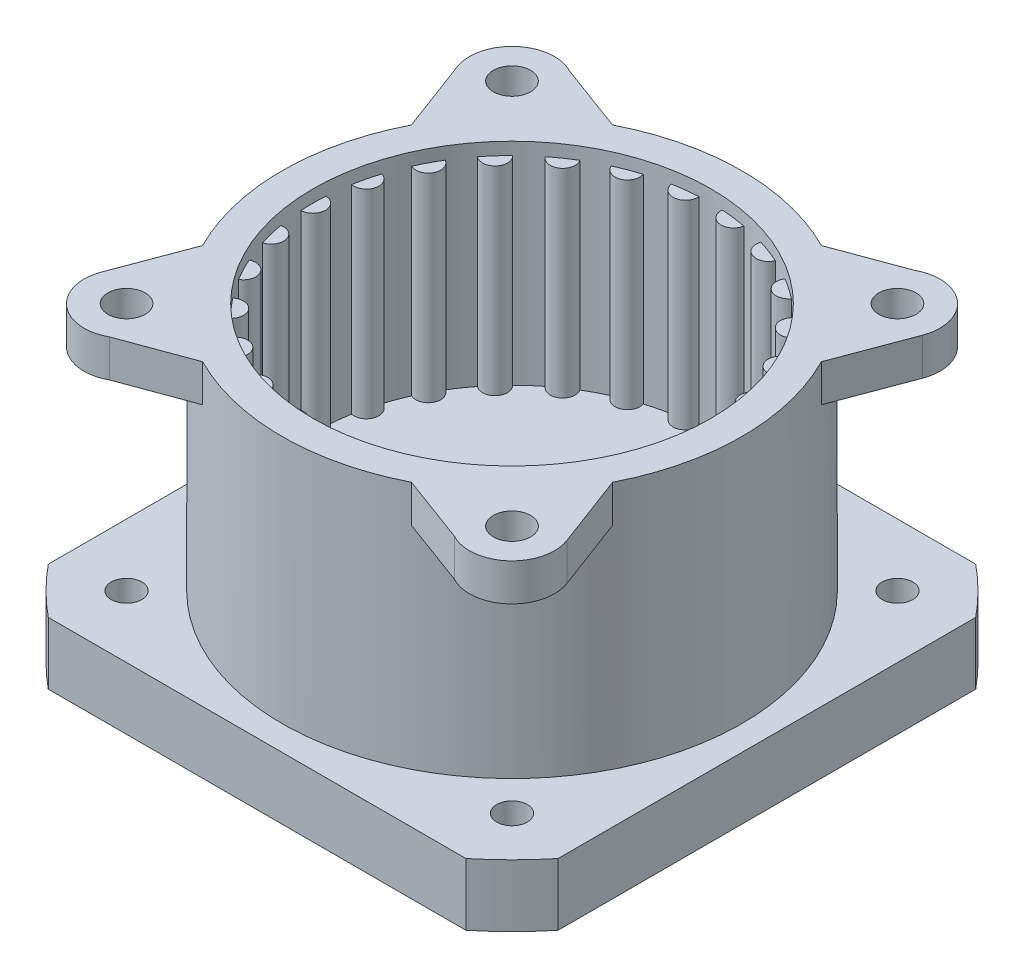
SolidWorks part; units mm, degrees
ref_plane "Front Plane" through (0, 0, 0) normal (0, 0, 1) x (1, 0, 0)
ref_plane "Top Plane" through (0, 0, 0) normal (0, 1, 0) x (1, 0, 0)
ref_plane "Right Plane" through (0, 0, 0) normal (1, 0, 0) x (0, 0, -1)
sketch "Sketch1" plane through (0, 0, 0) normal (0, 1, 0) x (1, 0, 0)
  circle A0 centre (15.5, 0) radius 1
  circle A1 centre (15.0351, -3.8291) radius 1
  circle A2 centre (13.6673, -7.4356) radius 1
  circle A3 centre (11.4762, -10.61) radius 1
  circle A4 centre (8.589, -13.1677) radius 1
  circle A5 centre (5.1737, -14.9603) radius 1
  circle A6 centre (1.4286, -15.8833) radius 1
  circle A7 centre (-2.4286, -15.8833) radius 1
  circle A8 centre (-6.1737, -14.9603) radius 1
  circle A9 centre (-9.589, -13.1677) radius 1
  circle A10 centre (-12.4762, -10.61) radius 1
  circle A11 centre (-14.6673, -7.4356) radius 1
  circle A12 centre (-16.0351, -3.8291) radius 1
  circle A13 centre (-16.5, 0) radius 1
  circle A14 centre (-16.0351, 3.8291) radius 1
  circle A15 centre (-14.6673, 7.4356) radius 1
  circle A16 centre (-12.4762, 10.61) radius 1
  circle A17 centre (-9.589, 13.1677) radius 1
  circle A18 centre (-6.1737, 14.9603) radius 1
  circle A19 centre (-2.4286, 15.8833) radius 1
  circle A20 centre (1.4286, 15.8833) radius 1
  circle A21 centre (5.1737, 14.9603) radius 1
  circle A22 centre (8.589, 13.1677) radius 1
  circle A23 centre (11.4762, 10.61) radius 1
  circle A24 centre (13.6673, 7.4356) radius 1
  circle A25 centre (15.0351, 3.8291) radius 1
  spline S0 degree 4 number of poles 315 (14.4, 0) -> (-15.4, 0) construction
sketch "Sketch2" plane through (0, 0, 0) normal (0, 1, 0) x (1, 0, 0)
  circle A0 centre (15.5, 0) radius 1
  circle A1 centre (15.0351, -3.8291) radius 1
  circle A2 centre (13.6673, -7.4356) radius 1
  circle A3 centre (11.4762, -10.61) radius 1
  circle A4 centre (8.589, -13.1677) radius 1
  circle A5 centre (5.1737, -14.9603) radius 1
  circle A6 centre (1.4286, -15.8833) radius 1
  circle A7 centre (-2.4286, -15.8833) radius 1
  circle A8 centre (-6.1737, -14.9603) radius 1
  circle A9 centre (-9.589, -13.1677) radius 1
  circle A10 centre (-12.4762, -10.61) radius 1
  circle A11 centre (-14.6673, -7.4356) radius 1
  circle A12 centre (-16.0351, -3.8291) radius 1
  circle A13 centre (-16.5, 0) radius 1
  circle A14 centre (-16.0351, 3.8291) radius 1
  circle A15 centre (-14.6673, 7.4356) radius 1
  circle A16 centre (-12.4762, 10.61) radius 1
  circle A17 centre (-9.589, 13.1677) radius 1
  circle A18 centre (-6.1737, 14.9603) radius 1
  circle A19 centre (-2.4286, 15.8833) radius 1
  circle A20 centre (1.4286, 15.8833) radius 1
  circle A21 centre (5.1737, 14.9603) radius 1
  circle A22 centre (8.589, 13.1677) radius 1
  circle A23 centre (11.4762, 10.61) radius 1
  circle A24 centre (13.6673, 7.4356) radius 1
  circle A25 centre (15.0351, 3.8291) radius 1
extrude "Boss-Extrude1" add sketch "Sketch2" along normal blind 8 and the other way blind 8
sketch "Sketch4" plane through (0, 0, 0) normal (0, 1, 0) x (1, 0, 0)
  line L0 (-15.4, 0) -> (14.4, 0) construction
  line L1 (0, 0) -> (0, 14.9128) construction
  line L2 (0, 0) -> (0, -14.9128) construction
  line L3 (0, 0) -> (-0.5, 0) construction
  line L4 (-0.5, 0) -> (-0.5, 15.3103) construction
  line L5 (-0.5, 0) -> (-0.5, -15.3103) construction
  line L6 (14.4, 0) -> (15.5, 0) construction
  line L7 (0, 0) -> (10, 0) construction
  line L8 (7.9, 0) -> (9.5, 0)
  line L9 (-0.5, 0) -> (9.5, 0) construction
  line L10 (-0.5, 15.3103) -> (-0.5, -15.3103) construction
  circle A0 centre (-0.5, 0) radius 16
  circle A1 centre (15.5, 0) radius 1
  circle A2 centre (15.0351, -3.8291) radius 1
  circle A3 centre (13.6673, -7.4356) radius 1
  circle A4 centre (11.4762, -10.61) radius 1
  circle A5 centre (8.589, -13.1677) radius 1
  circle A6 centre (5.1737, -14.9603) radius 1
  circle A7 centre (1.4286, -15.8833) radius 1
  circle A8 centre (-2.4286, -15.8833) radius 1
  circle A9 centre (-6.1737, -14.9603) radius 1
  circle A10 centre (-9.589, -13.1677) radius 1
  circle A11 centre (-12.4762, -10.61) radius 1
  circle A12 centre (-14.6673, -7.4356) radius 1
  circle A13 centre (-16.0351, -3.8291) radius 1
  circle A14 centre (-16.5, 0) radius 1
  circle A15 centre (-16.0351, 3.8291) radius 1
  circle A16 centre (-14.6673, 7.4356) radius 1
  circle A17 centre (-12.4762, 10.61) radius 1
  circle A18 centre (-9.589, 13.1677) radius 1
  circle A19 centre (-6.1737, 14.9603) radius 1
  circle A20 centre (-2.4286, 15.8833) radius 1
  circle A21 centre (1.4286, 15.8833) radius 1
  circle A22 centre (5.1737, 14.9603) radius 1
  circle A23 centre (8.589, 13.1677) radius 1
  circle A24 centre (11.4762, 10.61) radius 1
  circle A25 centre (13.6673, 7.4356) radius 1
  circle A26 centre (15.0351, 3.8291) radius 1
  circle A27 centre (0, 0) radius 10
  circle A28 centre (10, 0) radius 2.1
  circle A29 centre (5, -8.6603) radius 2.1
  circle A30 centre (-5, -8.6603) radius 2.1
  circle A31 centre (-10, 0) radius 2.1
  circle A32 centre (-5, 8.6603) radius 2.1
  circle A33 centre (5, 8.6603) radius 2.1
  circle A34 centre (-6, 8.6603) radius 2.1
  circle A35 centre (4, 8.6603) radius 2.1
  circle A36 centre (9, 0) radius 2.1
  circle A37 centre (4, -8.6603) radius 2.1
  circle A38 centre (-6, -8.6603) radius 2.1
  circle A39 centre (-1, 0) radius 10
  circle A40 centre (-11, 0) radius 2.1
  circle A41 centre (9.5, 0) radius 1.5
  circle A42 centre (4.5, -8.6603) radius 1.5
  circle A43 centre (-5.5, -8.6603) radius 1.5
  circle A44 centre (-10.5, 0) radius 1.5
  circle A45 centre (-5.5, 8.6603) radius 1.5
  circle A46 centre (4.5, 8.6603) radius 1.5
  circle A47 centre (-0.5, 0) radius 19.5
  circle A48 centre (0, 0) radius 5.55
  circle A49 centre (-0.5, 0) radius 5.55
  spline S0 degree 4 number of poles 369 (14.1521, 3.1658) -> (-14.9531, 3.4358) construction
  spline S1 degree 4 number of poles 315 (14.4, 0) -> (-15.4, 0)
  spline S2 degree 4 number of poles 315 (14.4, 0) -> (-15.4, 0)
  spline S3 degree 4 number of poles 315 (-15.4, 0) -> (14.4, 0)
  spline S4 degree 4 number of poles 315 (-15.4, 0) -> (14.4, 0)
  dimension "D1" = 32
  dimension "D2" = 2
  dimension "D4" = 20
  dimension "D5" = 4.2
  dimension "D8" = 6
  dimension "D7" = 10
  dimension "D9" = 10
  dimension "D3" = 26
  dimension "D6" = 6
sketch "Sketch5" plane through (0, 0, 0) normal (0, 1, 0) x (1, 0, 0)
  circle A0 centre (-0.5, 0) radius 16
  circle A1 centre (-0.5, 0) radius 18.5
extrude "Boss-Extrude3" add sketch "Sketch5" along normal blind 8 and the other way blind 8
sketch "Sketch6" plane through (0, 8, 0) normal (0, 1, 0) x (1, 0, 0)
  circle A0 centre (-0.5, 0) radius 18.5 construction
  circle A1 centre (-0.5, 0) radius 18.5
  circle A2 centre (-0.5, 0) radius 16
  dimension "D1" = 37
  dimension "D2" = 32
extrude "Boss-Extrude4" add sketch "Sketch6" along normal blind 1
sketch "Sketch7" plane through (0, 9, 0) normal (0, 1, 0) x (1, 0, 0)
  circle A0 centre (-0.5, 0) radius 18.5 construction
  circle A1 centre (-5.5, -8.6603) radius 1.5 construction
  circle A2 centre (4.5, -8.6603) radius 1.5 construction
  circle A3 centre (9.5, 0) radius 1.5 construction
  circle A4 centre (-10.5, 0) radius 1.5 construction
  circle A5 centre (-5.5, 8.6603) radius 1.5 construction
  circle A6 centre (4.5, 8.6603) radius 1.5 construction
  circle A7 centre (-0.5, 0) radius 18.5
  circle A8 centre (-5.5, -8.6603) radius 1.5
  circle A9 centre (4.5, -8.6603) radius 1.5
  circle A10 centre (9.5, 0) radius 1.5
  circle A11 centre (-10.5, 0) radius 1.5
  circle A12 centre (-5.5, 8.6603) radius 1.5
  circle A13 centre (4.5, 8.6603) radius 1.5
sketch "Sketch8" plane through (0, -8, 0) normal (0, -1, 0) x (1, 0, 0)
  circle A0 centre (-0.5, 0) radius 18.5
  dimension "D1" = 37
extrude "Boss-Extrude5" add sketch "Sketch8" along normal blind 3
sketch "Sketch9" plane through (0, -11, 0) normal (0, -1, 0) x (1, 0, 0)
  circle A0 centre (-0.5, 0) radius 6
  dimension "D1" = 12
extrude "Cut-Extrude1" cut sketch "Sketch9" against normal blind 3
ref_plane "Plane1" through (13.1751, 8, 8.3061) normal (0, -1, 0) x (-1, 0, 0)
sketch "Sketch13" plane through (0, -11, 0) normal (0, -1, 0) x (1, 0, 0)
  line L4 (-17.2929, -20.5) -> (16.2929, -20.5)
  line L5 (-21, 16.7929) -> (-21, -16.7929)
  line L6 (16.2929, 20.5) -> (-17.2929, 20.5)
  line L7 (20, -16.7929) -> (20, 16.7929)
  line L8 (-17.2929, -20.5) -> (16.2929, -20.5)
  line L9 (-21, 16.7929) -> (-21, -16.7929)
  line L10 (16.2929, 20.5) -> (-17.2929, 20.5)
  line L11 (20, -16.7929) -> (20, 16.7929)
  circle A0 centre (-16, -15.5) radius 1.23 construction
  circle A1 centre (15, -15.5) radius 1.23 construction
  circle A2 centre (15, 15.5) radius 1.23 construction
  circle A3 centre (-16, 15.5) radius 1.23 construction
  arc A4 (-21, -16.7929) -> (-17.2929, -20.5) centre (-0.5, 0) ccw
  arc A5 (-17.2929, 20.5) -> (-21, 16.7929) centre (-0.5, 0) ccw
  arc A6 (20, 16.7929) -> (16.2929, 20.5) centre (-0.5, 0) ccw
  arc A7 (16.2929, -20.5) -> (20, -16.7929) centre (-0.5, 0) ccw
  arc A8 (-21, -16.7929) -> (-17.2929, -20.5) centre (-0.5, 0) ccw
  arc A9 (-17.2929, 20.5) -> (-21, 16.7929) centre (-0.5, 0) ccw
  arc A10 (20, 16.7929) -> (16.2929, 20.5) centre (-0.5, 0) ccw
  arc A11 (16.2929, -20.5) -> (20, -16.7929) centre (-0.5, 0) ccw
  circle A12 centre (-16, -15.5) radius 1.23
  circle A13 centre (15, -15.5) radius 1.23
  circle A14 centre (15, 15.5) radius 1.23
  circle A15 centre (-16, 15.5) radius 1.23
  circle A16 centre (-0.5, 0) radius 6
  dimension "D1" = 0
extrude "Boss-Extrude7" add sketch "Sketch13" along normal blind 5
sketch "Sketch14" plane through (0, 9, 0) normal (0, 1, 0) x (1, 0, 0)
  line L0 (-16, 15.5) -> (15, -15.5) construction
  line L1 (-0.5, 20.5) -> (-0.5, -20.5) construction
  line L2 (-16, -15.5) -> (15, 15.5) construction
  line L3 (-17.2929, 20.5) -> (16.2929, 20.5) construction
  line L4 (16.2929, -20.5) -> (-17.2929, -20.5) construction
  line L5 (-0.5, 18.5) -> (12.5815, 13.0815) construction
  line L6 (-8.8938, 16.4862) -> (-14.3573, 18.5)
  line L7 (-21.5, 0) -> (20, 0) construction
  line L8 (-21.5, 16.9706) -> (-21.5, -16.9706) construction
  line L9 (20, 16.7929) -> (20, -16.7929) construction
  line L10 (12.5815, 13.0815) -> (18, 0) construction
  line L11 (7.8938, 16.4862) -> (13.3573, 18.5)
  line L12 (15.9862, 8.3938) -> (18.2022, 14.2982)
  line L13 (-16.9862, 8.3938) -> (-19.2022, 14.2982)
  line L14 (-16.9862, -8.3938) -> (-19.2022, -14.2982)
  line L15 (-8.8938, -16.4862) -> (-14.3573, -18.5)
  line L16 (7.8938, -16.4862) -> (13.3573, -18.5)
  line L17 (15.9862, -8.3938) -> (18.2022, -14.2982)
  circle A0 centre (15, 15.5) radius 1.5
  circle A1 centre (-16, -15.5) radius 1.5
  circle A2 centre (-16, 15.5) radius 1.5
  circle A3 centre (15, -15.5) radius 1.5
  circle A4 centre (-0.5, 0) radius 18.5 construction
  arc A5 (13.3573, 18.5) -> (18.2022, 14.2982) centre (15, 15.5) cw
  circle A7 centre (15, 15.5) radius 3.4203
  arc A8 (-14.3573, 18.5) -> (-19.2022, 14.2982) centre (-16, 15.5) ccw
  arc A9 (7.8938, 16.4862) -> (15.9862, 8.3938) centre (-0.5, 0) cw
  circle A10 centre (-16, 15.5) radius 1.5
  arc A11 (-8.8938, 16.4862) -> (-16.9862, 8.3938) centre (-0.5, 0) ccw
  circle A12 centre (-16, -15.5) radius 1.5
  arc A13 (-14.3573, -18.5) -> (-19.2022, -14.2982) centre (-16, -15.5) cw
  arc A14 (-8.8938, -16.4862) -> (-16.9862, -8.3938) centre (-0.5, 0) cw
  arc A15 (13.3573, -18.5) -> (18.2022, -14.2982) centre (15, -15.5) ccw
  circle A16 centre (15, -15.5) radius 1.5
  arc A17 (7.8938, -16.4862) -> (15.9862, -8.3938) centre (-0.5, 0) ccw
  circle M7 centre (-0.5, 0) radius 18.5
  dimension "D1" = 3
  dimension "D2" = 3
extrude "Boss-Extrude9" add sketch "Sketch14" against normal blind 3 contours A7 L12 M7 | A7 L11 M7 | A5 A7 A0 | L6 A8 L13 A2 M7 | A13 L15 L14 A1 M7 | L16 A15 L17 A3 M7 region at (-13.6867, 9, -13.1867) region at (10.6325, 9, -16.2539) region at (-13.6867, 9, 13.1867) region at (16.6942, 9, -18.3593) region at (15.7753, 9, -11.1457) region at (12.6867, 9, 13.1867)
